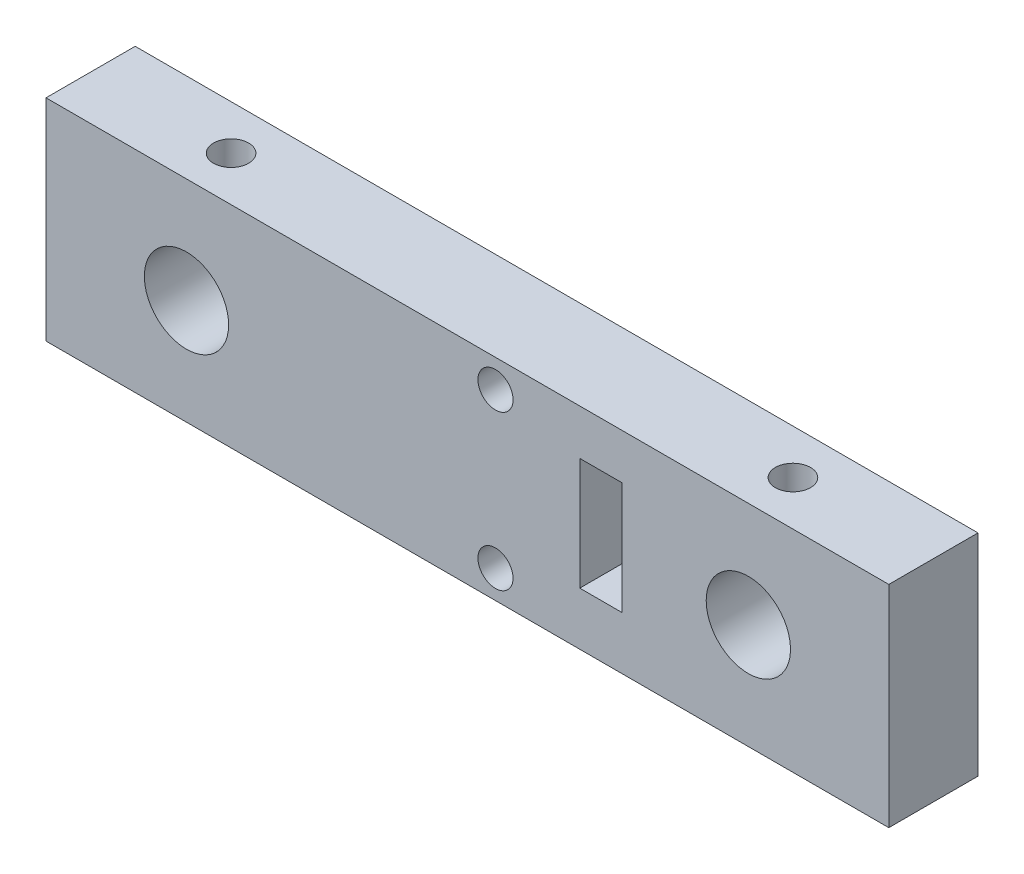
SolidWorks part; units mm, degrees
material "6061 Alloy"
ref_plane "Front Plane" through (0, 0, 0) normal (0, 0, 1) x (1, 0, 0)
ref_plane "Top Plane" through (0, 0, 0) normal (0, 1, 0) x (1, 0, 0)
ref_plane "Right Plane" through (0, 0, 0) normal (1, 0, 0) x (0, 0, -1)
sketch "Sketch1" plane through (0, 0, 0) normal (0, 0, 1) x (1, 0, 0)
  line L0 (30, 15) -> (30, 0) construction
  line L1 (0, 0) -> (60, 0)
  line L2 (0, 0) -> (0, 15)
  line L3 (0, 15) -> (60, 15)
  line L4 (60, 0) -> (60, 15)
  line L5 (0, 7.5) -> (60, 7.5) construction
  circle A0 centre (10, 7.5) radius 3
  circle A1 centre (50, 7.5) radius 3
  dimension "D3" = 6
  dimension "D1" = 60
  dimension "D2" = 15
  dimension "D4" = 40
extrude "Boss-Extrude1" add sketch "Sketch1" along normal blind 6.35
ref_axis "Axis1" through (10, 7.5, 6.35) along (0, 0, -1)
hole_wizard "M3 Tapped Hole1" positions "Sketch4" profile "Sketch3" tap size "M3" standard "ISO"
sketch "Sketch4" plane through (0, 15, 0) normal (0, 1, 0) x (-1, 0, 0)
  line L0 (0, 3.175) -> (-60, 3.175) construction
  line L1 (0, 6.35) -> (0, 0) construction
  line L2 (-60, 6.35) -> (-60, 0) construction
  line L5 (-30, 0) -> (-30, 6.35) construction
  line L6 (-60, 0) -> (0, 0) construction
  line L7 (-60, 6.35) -> (0, 6.35) construction
  line L10 (-10, 6.35) -> (-10, 0) construction
  point P0 (-10, 3.175)
  point P25 (-50, 3.175)
sketch "Sketch3" plane through (10, 15, 3.175) normal (1, 0, 0) x (0, 0, 1)
  line L0 (0, 0) -> (0, 9.2511)
  line L1 (0, 9.2511) -> (1.25, 8.5)
  line L2 (1.25, 8.5) -> (1.25, 0)
  line L5 (1.25, 0) -> (0, 0)
  line L10 (0, 9.2511) -> (-1.25, 8.5) construction
  line L11 (0, -6.35) -> (0, 107.95) construction
  dimension "Tap Drill Dia." = 2.5
  dimension "Tap Drill Depth" = 8.5
  dimension "Drill Angle" = 118
cosmetic thread "Hole Thread1" parameters "D1"=4.8642, "D2"=3
cosmetic thread "Hole Thread2" parameters "D1"=4.8642, "D2"=3
ref_plane "Center plane" through (30, 0, 0) normal (-1, 0, 0) x (0, 0, 1)
ref_plane "Belt plane" through (39, 0, 0) normal (1, 0, 0) x (0, 0, -1)
sketch "Sketch5" plane through (0, 0, 6.35) normal (0, 0, 1) x (1, 0, 0)
  line L1 (38, 11.7693) -> (41, 11.7693)
  line L2 (38, 11.7693) -> (38, 3.7693)
  line L3 (38, 3.7693) -> (41, 3.7693)
  line L4 (41, 11.7693) -> (41, 3.7693)
  line L5 (39, -3.4925) -> (39, 3.4925) construction
  dimension "D1" = 3
  dimension "D2" = 1
  dimension "D3" = 8
extrude "Cut-Extrude1" cut sketch "Sketch5" against normal through all
hole_wizard "M3 Tapped Hole2" positions "Sketch7" profile "Sketch8" tap size "M3" standard "ISO" end condition through all
sketch "Sketch7" plane through (0, 0, 6.35) normal (0, 0, 1) x (1, 0, 0)
  line L0 (60, 7.5) -> (28.002, 7.5) construction
  line L1 (60, 0) -> (60, 15) construction
  line L3 (32, 15) -> (32, 0) construction
  line L4 (60, 15) -> (0, 15) construction
  line L5 (0, 0) -> (60, 0) construction
  point P0 (32, 13)
  point P18 (32, 2)
  dimension "D1" = 28
  dimension "D2" = 11
sketch "Sketch8" plane through (32, 13, 6.35) normal (1, 0, 0) x (0, -1, 0)
  line L0 (0, 0) -> (0, 6.35)
  line L1 (0, 6.35) -> (1.25, 6.35)
  line L2 (1.25, 6.35) -> (1.25, 0)
  line L5 (1.25, 0) -> (0, 0)
  line L11 (0, -6.35) -> (0, 107.95) construction
  dimension "Thru Tap Drill Dia." = 2.5
  dimension "Thru Tap Drill Depth" = 6.35
cosmetic thread "Hole Thread3" parameters "D2"=3
cosmetic thread "Hole Thread4" parameters "D2"=3
